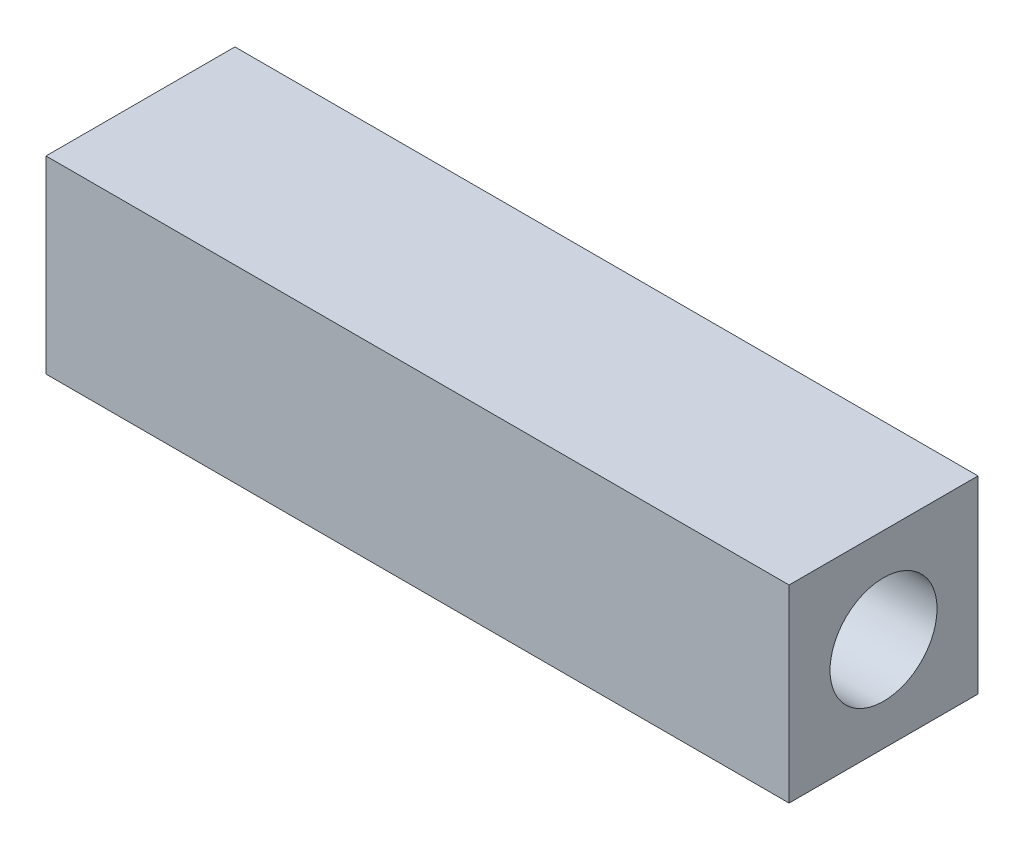
SolidWorks part; units mm, degrees
ref_plane "Front Plane" through (0, 0, 0) normal (0, 0, 1) x (1, 0, 0)
ref_plane "Top Plane" through (0, 0, 0) normal (0, 1, 0) x (1, 0, 0)
ref_plane "Right Plane" through (0, 0, 0) normal (1, 0, 0) x (0, 0, -1)
sketch "Sketch1" plane through (0, 0, 0) normal (1, 0, 0) x (0, 0, -1)
  line L1 (15, -15) -> (-15, -15)
  line L2 (15, -15) -> (15, 15)
  line L3 (15, 15) -> (-15, 15)
  line L4 (-15, -15) -> (-15, 15)
  line L5 (15, -15) -> (-15, 15) construction
  line L6 (15, 15) -> (-15, -15) construction
  point P0 (0, 0)
  dimension "D1" = 30
  dimension "D2" = 30
extrude "Boss-Extrude1" add sketch "Sketch1" along normal blind 118
sketch "Sketch2" plane through (118, 0, 0) normal (1, 0, 0) x (0, 0, -1)
  circle A0 centre (0, 0) radius 8.5
  dimension "D1" = 17
extrude "Cut-Extrude1" cut sketch "Sketch2" against normal blind 19
sketch "Sketch3" plane through (99, 0, 0) normal (1, 0, 0) x (0, 0, -1)
  circle A1 centre (0, 0) radius 9
  dimension "D1" = 18
extrude "Cut-Extrude2" cut sketch "Sketch3" against normal blind 26
sketch "Sketch4" plane through (73, 0, 0) normal (1, 0, 0) x (0, 0, -1)
  circle A0 centre (0, 0) radius 10
  dimension "D1" = 20
extrude "Cut-Extrude3" cut sketch "Sketch4" against normal blind 32
sketch "Sketch5" plane through (41, 0, 0) normal (1, 0, 0) x (0, 0, -1)
  circle A0 centre (0, 0) radius 8.5
  dimension "D1" = 17
extrude "Cut-Extrude4" cut sketch "Sketch5" against normal blind 44
fillet "Fillet3" radius 10 1 edges at (41, 0, -8.5)
fillet "Fillet4" radius 3 1 edges at (41, 0, -10)
fillet "Fillet5" radius 3 1 edges at (73, 0, -9)
fillet "Fillet6" radius 3 1 edges at (73, 0, -10)
fillet "Fillet7" radius 3 1 edges at (99, 0, -8.5)
fillet "Fillet8" radius 3 1 edges at (99, 0, -9)
